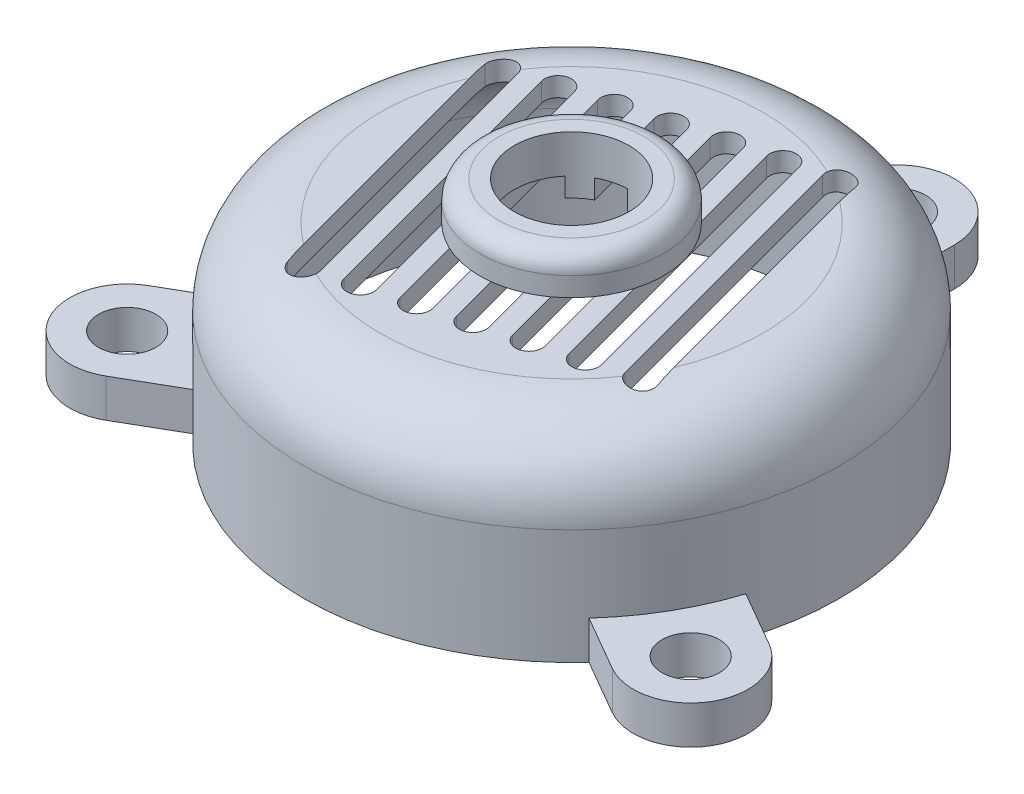
SolidWorks part; units mm, degrees
ref_plane "Front Plane" through (0, 0, 0) normal (0, 0, 1) x (1, 0, 0)
ref_plane "Top Plane" through (0, 0, 0) normal (0, 1, 0) x (1, 0, 0)
ref_plane "Right Plane" through (0, 0, 0) normal (1, 0, 0) x (0, 0, -1)
sketch "Sketch1" plane through (0, 0, 0) normal (0, 0, 1) x (1, 0, 0)
  line L0 (0, 0) -> (0, 30) construction
  line L1 (7.5, 30) -> (9.5, 30)
  line L2 (12, 27.5) -> (12, 25)
  line L3 (12, 25) -> (25, 25)
  line L4 (35, 15) -> (35, 0)
  line L5 (7.5, 30) -> (7.5, 22.5)
  line L6 (7.5, 30) -> (0, 30) construction
  line L7 (7.5, 30) -> (7.5, 18.2301) construction
  line L8 (10, 22.5) -> (10, 22.5)
  line L9 (10, 22.5) -> (10, 22.5)
  line L10 (10, 22.5) -> (25, 22.5)
  line L11 (32.5, 15) -> (32.5, 0)
  line L12 (10, 22.5) -> (10, 18.2301) construction
  line L13 (7.5, 22.5) -> (10, 22.5)
  line L14 (35, 0) -> (32.5, 0)
  arc A0 (25, 25) -> (35, 15) centre (25, 15) cw
  arc A1 (9.5, 30) -> (12, 27.5) centre (9.5, 27.5) cw
  arc A2 (10, 22.5) -> (10, 22.5) centre (10, 22.5) cw
  arc A3 (25, 22.5) -> (32.5, 15) centre (25, 15) cw
  point P3 (10, 22.5)
  point P14 (12, 30)
  dimension "D6" = 10
  dimension "D7" = 2.5
  dimension "D1" = 30
  dimension "D2" = 25
  dimension "D3" = 12
  dimension "D4" = 7.5
  dimension "D5" = 35
  dimension "D8" = 2.5
revolve "Revolve1" add sketch "Sketch1" angle 360 about L0
sketch "Sketch2" plane through (0, 0, 0) normal (0, 1, 0) x (1, 0, 0)
  line L0 (0, 0) -> (0, 42.5) construction
  line L1 (-7.5, 42.5) -> (-7.5, 34.187)
  line L2 (7.5, 42.5) -> (7.5, 34.187)
  line L3 (40.5561, -14.7548) -> (33.3568, -10.5983)
  line L4 (33.0561, -27.7452) -> (25.8568, -23.5887)
  line L5 (-33.0561, -27.7452) -> (-25.8568, -23.5887)
  line L6 (-40.5561, -14.7548) -> (-33.3568, -10.5983)
  circle A0 centre (0, 42.5) radius 3.75
  circle A2 centre (0, 0) radius 35 construction
  arc A3 (7.5, 34.187) -> (-7.5, 34.187) centre (0, 0) ccw
  arc A4 (7.5, 42.5) -> (-7.5, 42.5) centre (0, 42.5) ccw
  arc A5 (25.8568, -23.5887) -> (33.3568, -10.5983) centre (0, 0) ccw
  arc A6 (33.0561, -27.7452) -> (40.5561, -14.7548) centre (36.8061, -21.25) ccw
  arc A7 (-33.3568, -10.5983) -> (-25.8568, -23.5887) centre (0, 0) ccw
  arc A8 (-40.5561, -14.7548) -> (-33.0561, -27.7452) centre (-36.8061, -21.25) ccw
  circle A9 centre (36.8061, -21.25) radius 3.75
  circle A10 centre (-36.8061, -21.25) radius 3.75
  point P4 (0, 0)
  point P11 (0, 50)
  point P23 (0, 0)
  point P27 (0, 0)
  dimension "D2" = 7.5
  dimension "D3" = 7.5
  dimension "D1" = 42.5
  dimension "D4" = 3
  dimension "D5" = 3
extrude "Boss-Extrude1" add sketch "Sketch2" along normal blind 5
sketch "Sketch3" plane through (0, 25, 0) normal (0, 1, 0) x (1, 0, 0)
  line L0 (0, 0) -> (0, 42.5) construction
  line L1 (0, 0) -> (-11.7315, 43.7824) construction
  line L2 (-5.1764, 19.3185) -> (-22.563, 14.6598) construction
  line L3 (-22.563, 14.6598) -> (-12.8632, -21.5404) construction
  line L5 (-23.8005, 12.5165) -> (-14.3536, -22.7398)
  line L6 (-20.4197, 13.4223) -> (-10.9728, -21.834)
  line L8 (0, 0) -> (-19.077, -5.1117) construction
  arc A1 (-10.9728, -21.834) -> (-14.3536, -22.7398) centre (-12.6632, -22.2869) cw
  arc A4 (-20.4197, 13.4223) -> (-23.8005, 12.5165) centre (-22.1101, 12.9694) ccw
  point P7 (0, 0)
  point P16 (-21.9183, 14.8325)
  point P17 (-19.7668, 10.9855)
  point P18 (-22.563, 14.6598)
  dimension "D5" = 20
  dimension "D2" = 18
  dimension "D1" = 15
  dimension "D3" = 1.75
sketch "Sketch4" plane through (0, 25, 0) normal (0, 1, 0) x (1, 0, 0)
  line L0 (0, 0) -> (0, 32.4667) construction
  line L1 (0, 0) -> (-8.1052, 30.249) construction
  line L2 (0, 0) -> (-37.4608, -10.0376) construction
  dimension "D1" = 15
  dimension "D2" = 90
extrude "Cut-Extrude2" cut sketch "Sketch3" against normal up to surface (25.001 mm away) up to face at (0, 15, -32.5)
pattern_linear "LPattern2" count 7 spacing 6 along (0.9659, 0, -0.2588) of "Cut-Extrude2"
